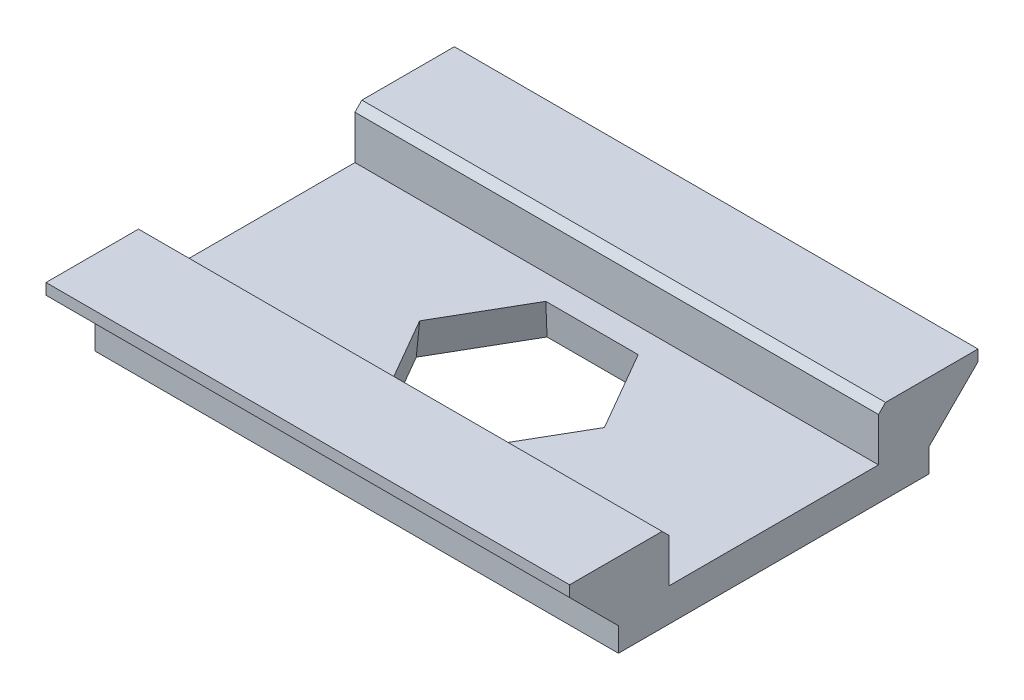
SolidWorks part; units mm, degrees
ref_plane "Front Plane" through (0, 0, 0) normal (0, 0, 1) x (1, 0, 0)
ref_plane "Top Plane" through (0, 0, 0) normal (0, 1, 0) x (1, 0, 0)
ref_plane "Right Plane" through (0, 0, 0) normal (1, 0, 0) x (0, 0, -1)
sketch "Retainer Profile" plane through (0, 0, 0) normal (1, 0, 0) x (0, 0, -1)
  line L1 (-4.65, 2.9923) -> (-4.65, 2.3923) construction
  line L2 (-6.05, 4.3923) -> (-4.65, 2.9923) construction
  line L8 (-6.05, 4.9923) -> (-6.05, 4.3923) construction
  line L9 (-5.05, 4.9923) -> (-6.05, 4.9923) construction
  line L10 (-4.65, 2.9923) -> (-4.65, 2.3923) construction
  line L11 (-6.05, 4.3923) -> (-4.65, 2.9923) construction
  line L23 (0, -28.6883) -> (0, 28.6883) construction
  line L24 (0, -28.6883) -> (0, 28.6883) construction
  line L27 (-6.05, 4.9923) -> (-6.05, 4.3923) construction
  line L28 (-5.05, 4.9923) -> (-6.05, 4.9923) construction
  line L31 (-5.05, 4.7923) -> (-5.85, 4.7923)
  line L32 (-5.85, 4.7923) -> (-5.85, 4.4751)
  line L33 (-5.85, 4.4751) -> (-4.45, 3.0751)
  line L34 (-4.45, 3.0751) -> (-4.45, 2.3923)
  line L35 (-5.05, 4.7923) -> (-3, 4.7923)
  line L36 (-3, 4.7923) -> (-3, 3.3423)
  line L37 (-3, 3.3423) -> (3, 3.3423)
  line L38 (-4.45, 2.3923) -> (4.45, 2.3923)
  line L39 (3, 4.7923) -> (3, 3.3423)
  line L40 (5.05, 4.7923) -> (3, 4.7923)
  line L41 (4.45, 3.0751) -> (4.45, 2.3923)
  line L42 (5.85, 4.4751) -> (4.45, 3.0751)
  line L43 (5.85, 4.7923) -> (5.85, 4.4751)
  line L44 (5.05, 4.7923) -> (5.85, 4.7923)
  point P15 (0, 2.3923)
  point P16 (0, 3.3423)
  dimension "D3" = 3
  dimension "D1" = 0.2
  dimension "D2" = 1.45
extrude "Boss-Extrude1" add sketch "Retainer Profile" along normal mid plane 15
sketch "Sketch3" plane through (0, 4.7923, 0) normal (0, 1, 0) x (1, 0, 0)
  line L1 (2.5, 0) -> (1.25, 2.1651)
  line L2 (1.25, 2.1651) -> (-1.25, 2.1651)
  line L3 (-1.25, 2.1651) -> (-2.5, 0)
  line L4 (-2.5, 0) -> (-1.25, -2.1651)
  line L5 (-1.25, -2.1651) -> (1.25, -2.1651)
  line L6 (1.25, -2.1651) -> (2.5, 0)
  circle A0 centre (0, 0) radius 2.1651 construction
  dimension "D1" = 5
extrude "Cut-Extrude2" cut sketch "Sketch3" against normal through all draft 5 draft outward yes
chamfer "Chamfer1" distance 0.2 angle 45 2 edges at (0, 4.7923, 3) (0, 4.7923, -3)
